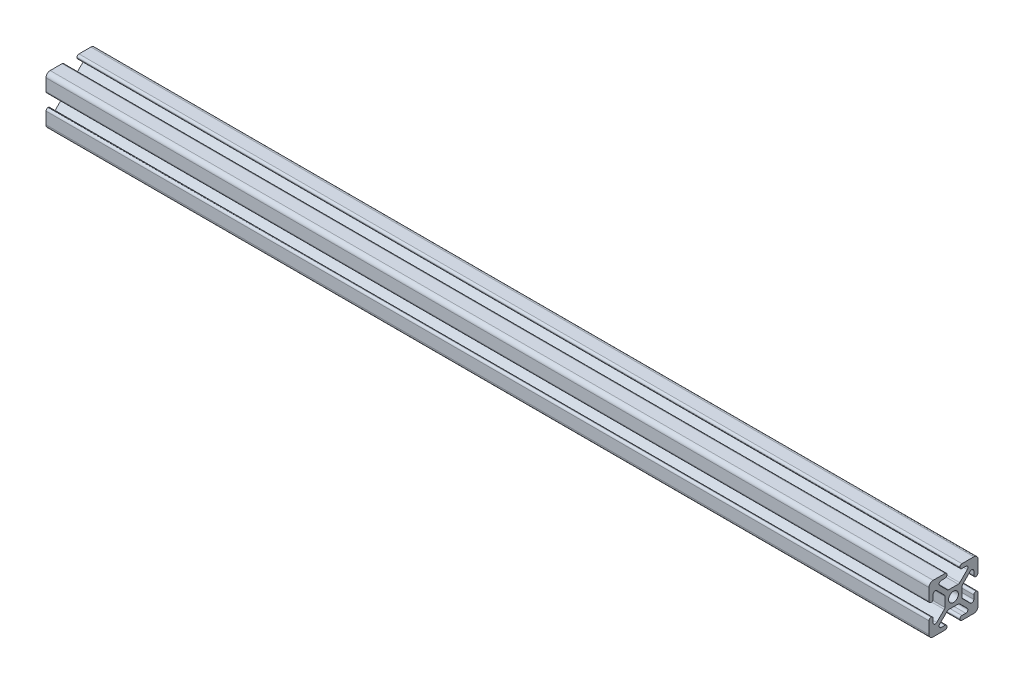
SolidWorks part; units mm, degrees
ref_plane "Front Plane" through (0, 0, 0) normal (1, 0, 0) x (0, 1, 0)
ref_plane "Top Plane" through (0, 0, 0) normal (0, 0, 1) x (0, 1, 0)
ref_plane "Right Plane" through (0, 0, 0) normal (0, 1, 0) x (-1, 0, 0)
sketch "Sketch1" plane through (0, 0, 0) normal (1, 0, 0) x (0, 1, 0)
  line L0 (0, 0) -> (0, 12.5) construction
  line L1 (-12.5, -12.5) -> (12.5, -12.5)
  line L2 (-12.5, -12.5) -> (-12.5, 12.5)
  line L3 (-12.5, 12.5) -> (12.5, 12.5)
  line L4 (12.5, -12.5) -> (12.5, 12.5)
  line L5 (-12.5, -12.5) -> (12.5, 12.5) construction
  line L6 (-12.5, 12.5) -> (12.5, -12.5) construction
  line L7 (-3.25, 12.5) -> (-3.25, 10.37)
  line L8 (-3.25, 10.37) -> (-8.8639, 10.37)
  line L9 (-8.8639, 10.37) -> (-2.8739, 4.38)
  line L10 (-2.8739, 4.38) -> (2.8739, 4.38)
  line L11 (8.8639, 10.37) -> (2.8739, 4.38)
  line L12 (3.25, 10.37) -> (8.8639, 10.37)
  line L13 (3.25, 12.5) -> (3.25, 10.37)
  line L14 (12.5, -3.25) -> (10.37, -3.25)
  line L15 (10.37, -3.25) -> (10.37, -8.8639)
  line L16 (10.37, -8.8639) -> (4.38, -2.8739)
  line L17 (4.38, 2.8739) -> (4.38, -2.8739)
  line L18 (10.37, 8.8639) -> (4.38, 2.8739)
  line L19 (10.37, 3.25) -> (10.37, 8.8639)
  line L20 (12.5, 3.25) -> (10.37, 3.25)
  line L21 (-3.25, -12.5) -> (-3.25, -10.37)
  line L22 (-3.25, -10.37) -> (-8.8639, -10.37)
  line L23 (-8.8639, -10.37) -> (-2.8739, -4.38)
  line L24 (2.8739, -4.38) -> (-2.8739, -4.38)
  line L25 (8.8639, -10.37) -> (2.8739, -4.38)
  line L26 (3.25, -10.37) -> (8.8639, -10.37)
  line L27 (3.25, -12.5) -> (3.25, -10.37)
  line L28 (-12.5, 3.25) -> (-10.37, 3.25)
  line L29 (-10.37, 3.25) -> (-10.37, 8.8639)
  line L30 (-10.37, 8.8639) -> (-4.38, 2.8739)
  line L31 (-4.38, -2.8739) -> (-4.38, 2.8739)
  line L32 (-10.37, -8.8639) -> (-4.38, -2.8739)
  line L33 (-10.37, -3.25) -> (-10.37, -8.8639)
  line L34 (-12.5, -3.25) -> (-10.37, -3.25)
  circle A0 centre (0, 0) radius 2.5
  point P0 (0, 0)
  point P15 (0, 4.38)
  dimension "D3" = 5
  dimension "D1" = 25
  dimension "D2" = 25
  dimension "D4" = 2.13
  dimension "D5" = 2.13
  dimension "D6" = 6.5
  dimension "D7" = 4.38
  dimension "D8" = 4
extrude "Boss-Extrude1" add sketch "Sketch1" along normal blind 450 contours L34 L2 L1 L21 L22 L23 L24 L25 L26 L27 L4 L14 L15 L16 L17 L18 L19 L20 L3 L13 L12 L11 L10 L9 L8 L7 L28 L29 L30 L31 L32 L33 A0 region at (0, -12.1464, -7.875)
fillet "Fillet1" radius 1.065 32 edges at (225, -10.37, -8.8639) (225, 2.8739, -4.38) (225, -2.8739, -4.38) (225, -4.38, 2.8739) (225, -4.38, -2.8739) (225, -2.8739, 4.38) (225, 2.8739, 4.38) (225, 4.38, 2.8739) (225, 4.38, -2.8739) (225, -8.8639, -10.37) (225, 8.8639, -10.37) (225, 10.37, -8.8639) (225, -10.37, 8.8639) (225, -8.8639, 10.37) (225, 10.37, 8.8639) (225, 8.8639, 10.37) (225, 12.5, 3.25) (225, -3.25, -12.5) (225, -10.37, 3.25) (225, 10.37, 3.25) (225, -10.37, -3.25) (225, -12.5, -3.25) (225, -12.5, 3.25) (225, 3.25, -10.37) (225, -3.25, -10.37) (225, 3.25, -12.5) (225, 10.37, -3.25) (225, 12.5, -3.25) (225, 3.25, 12.5) (225, 3.25, 10.37) (225, -3.25, 10.37) (225, -3.25, 12.5)
fillet "Fillet2" radius 2.13 4 edges at (225, 12.5, -12.5) (225, -12.5, -12.5) (225, 12.5, 12.5) (225, -12.5, 12.5)
sketch "Sketch2" plane through (450, 0, 0) normal (1, 0, 0) x (0, 1, 0)
  line L0 (10.37, -12.5) -> (4.315, -12.5)
  line L1 (10.37, -12.5) -> (4.315, -12.5)
  line L2 (4.315, -10.37) -> (6.2927, -10.37)
  line L3 (4.315, -10.37) -> (6.2927, -10.37)
  line L4 (7.0458, -8.5519) -> (3.1858, -4.6919)
  line L5 (7.0458, -8.5519) -> (3.1858, -4.6919)
  line L6 (2.4327, -4.38) -> (-2.4327, -4.38)
  line L7 (2.4327, -4.38) -> (-2.4327, -4.38)
  line L8 (-3.1858, -4.6919) -> (-7.0458, -8.5519)
  line L9 (-3.1858, -4.6919) -> (-7.0458, -8.5519)
  line L10 (-6.2927, -10.37) -> (-4.315, -10.37)
  line L11 (-6.2927, -10.37) -> (-4.315, -10.37)
  line L12 (-4.315, -12.5) -> (-10.37, -12.5)
  line L13 (-4.315, -12.5) -> (-10.37, -12.5)
  line L14 (-12.5, -10.37) -> (-12.5, -4.315)
  line L15 (-12.5, -10.37) -> (-12.5, -4.315)
  line L16 (-10.37, -4.315) -> (-10.37, -6.2927)
  line L17 (-10.37, -4.315) -> (-10.37, -6.2927)
  line L18 (-8.5519, -7.0458) -> (-4.6919, -3.1858)
  line L19 (-8.5519, -7.0458) -> (-4.6919, -3.1858)
  line L20 (-4.38, -2.4327) -> (-4.38, 2.4327)
  line L21 (-4.38, -2.4327) -> (-4.38, 2.4327)
  line L22 (-4.6919, 3.1858) -> (-8.5519, 7.0458)
  line L23 (-4.6919, 3.1858) -> (-8.5519, 7.0458)
  line L24 (-10.37, 6.2927) -> (-10.37, 4.315)
  line L25 (-10.37, 6.2927) -> (-10.37, 4.315)
  line L26 (-12.5, 4.315) -> (-12.5, 10.37)
  line L27 (-12.5, 4.315) -> (-12.5, 10.37)
  line L28 (-10.37, 12.5) -> (-4.315, 12.5)
  line L29 (-10.37, 12.5) -> (-4.315, 12.5)
  line L30 (-4.315, 10.37) -> (-6.2927, 10.37)
  line L31 (-4.315, 10.37) -> (-6.2927, 10.37)
  line L32 (-7.0458, 8.5519) -> (-3.1858, 4.6919)
  line L33 (-7.0458, 8.5519) -> (-3.1858, 4.6919)
  line L34 (-2.4327, 4.38) -> (2.4327, 4.38)
  line L35 (-2.4327, 4.38) -> (2.4327, 4.38)
  line L36 (3.1858, 4.6919) -> (7.0458, 8.5519)
  line L37 (3.1858, 4.6919) -> (7.0458, 8.5519)
  line L38 (6.2927, 10.37) -> (4.315, 10.37)
  line L39 (6.2927, 10.37) -> (4.315, 10.37)
  line L40 (4.315, 12.5) -> (10.37, 12.5)
  line L41 (4.315, 12.5) -> (10.37, 12.5)
  line L42 (12.5, 10.37) -> (12.5, 4.315)
  line L43 (12.5, 10.37) -> (12.5, 4.315)
  line L44 (10.37, 4.315) -> (10.37, 6.2927)
  line L45 (10.37, 4.315) -> (10.37, 6.2927)
  line L46 (8.5519, 7.0458) -> (4.6919, 3.1858)
  line L47 (8.5519, 7.0458) -> (4.6919, 3.1858)
  line L48 (4.38, 2.4327) -> (4.38, -2.4327)
  line L49 (4.38, 2.4327) -> (4.38, -2.4327)
  line L50 (4.6919, -3.1858) -> (8.5519, -7.0458)
  line L51 (4.6919, -3.1858) -> (8.5519, -7.0458)
  line L52 (10.37, -6.2927) -> (10.37, -4.315)
  line L53 (10.37, -6.2927) -> (10.37, -4.315)
  line L54 (12.5, -4.315) -> (12.5, -10.37)
  line L55 (12.5, -4.315) -> (12.5, -10.37)
  arc A0 (10.37, -12.5) -> (12.5, -10.37) centre (10.37, -10.37) ccw
  circle A1 centre (0, 0) radius 2.5
  circle A2 centre (0, 0) radius 2.5
  arc A3 (10.37, -12.5) -> (12.5, -10.37) centre (10.37, -10.37) ccw
  arc A4 (3.25, -11.435) -> (4.315, -12.5) centre (4.315, -11.435) ccw
  arc A5 (3.25, -11.435) -> (4.315, -12.5) centre (4.315, -11.435) ccw
  arc A6 (4.315, -10.37) -> (3.25, -11.435) centre (4.315, -11.435) ccw
  arc A7 (4.315, -10.37) -> (3.25, -11.435) centre (4.315, -11.435) ccw
  arc A8 (6.2927, -10.37) -> (7.0458, -8.5519) centre (6.2927, -9.305) ccw
  arc A9 (6.2927, -10.37) -> (7.0458, -8.5519) centre (6.2927, -9.305) ccw
  arc A10 (3.1858, -4.6919) -> (2.4327, -4.38) centre (2.4327, -5.445) ccw
  arc A11 (3.1858, -4.6919) -> (2.4327, -4.38) centre (2.4327, -5.445) ccw
  arc A12 (-2.4327, -4.38) -> (-3.1858, -4.6919) centre (-2.4327, -5.445) ccw
  arc A13 (-2.4327, -4.38) -> (-3.1858, -4.6919) centre (-2.4327, -5.445) ccw
  arc A14 (-7.0458, -8.5519) -> (-6.2927, -10.37) centre (-6.2927, -9.305) ccw
  arc A15 (-7.0458, -8.5519) -> (-6.2927, -10.37) centre (-6.2927, -9.305) ccw
  arc A16 (-3.25, -11.435) -> (-4.315, -10.37) centre (-4.315, -11.435) ccw
  arc A17 (-3.25, -11.435) -> (-4.315, -10.37) centre (-4.315, -11.435) ccw
  arc A18 (-4.315, -12.5) -> (-3.25, -11.435) centre (-4.315, -11.435) ccw
  arc A19 (-4.315, -12.5) -> (-3.25, -11.435) centre (-4.315, -11.435) ccw
  arc A20 (-12.5, -10.37) -> (-10.37, -12.5) centre (-10.37, -10.37) ccw
  arc A21 (-12.5, -10.37) -> (-10.37, -12.5) centre (-10.37, -10.37) ccw
  arc A22 (-11.435, -3.25) -> (-12.5, -4.315) centre (-11.435, -4.315) ccw
  arc A23 (-11.435, -3.25) -> (-12.5, -4.315) centre (-11.435, -4.315) ccw
  arc A24 (-10.37, -4.315) -> (-11.435, -3.25) centre (-11.435, -4.315) ccw
  arc A25 (-10.37, -4.315) -> (-11.435, -3.25) centre (-11.435, -4.315) ccw
  arc A26 (-10.37, -6.2927) -> (-8.5519, -7.0458) centre (-9.305, -6.2927) ccw
  arc A27 (-10.37, -6.2927) -> (-8.5519, -7.0458) centre (-9.305, -6.2927) ccw
  arc A28 (-4.6919, -3.1858) -> (-4.38, -2.4327) centre (-5.445, -2.4327) ccw
  arc A29 (-4.6919, -3.1858) -> (-4.38, -2.4327) centre (-5.445, -2.4327) ccw
  arc A30 (-4.38, 2.4327) -> (-4.6919, 3.1858) centre (-5.445, 2.4327) ccw
  arc A31 (-4.38, 2.4327) -> (-4.6919, 3.1858) centre (-5.445, 2.4327) ccw
  arc A32 (-8.5519, 7.0458) -> (-10.37, 6.2927) centre (-9.305, 6.2927) ccw
  arc A33 (-8.5519, 7.0458) -> (-10.37, 6.2927) centre (-9.305, 6.2927) ccw
  arc A34 (-11.435, 3.25) -> (-10.37, 4.315) centre (-11.435, 4.315) ccw
  arc A35 (-11.435, 3.25) -> (-10.37, 4.315) centre (-11.435, 4.315) ccw
  arc A36 (-12.5, 4.315) -> (-11.435, 3.25) centre (-11.435, 4.315) ccw
  arc A37 (-12.5, 4.315) -> (-11.435, 3.25) centre (-11.435, 4.315) ccw
  arc A38 (-10.37, 12.5) -> (-12.5, 10.37) centre (-10.37, 10.37) ccw
  arc A39 (-10.37, 12.5) -> (-12.5, 10.37) centre (-10.37, 10.37) ccw
  arc A40 (-3.25, 11.435) -> (-4.315, 12.5) centre (-4.315, 11.435) ccw
  arc A41 (-3.25, 11.435) -> (-4.315, 12.5) centre (-4.315, 11.435) ccw
  arc A42 (-4.315, 10.37) -> (-3.25, 11.435) centre (-4.315, 11.435) ccw
  arc A43 (-4.315, 10.37) -> (-3.25, 11.435) centre (-4.315, 11.435) ccw
  arc A44 (-6.2927, 10.37) -> (-7.0458, 8.5519) centre (-6.2927, 9.305) ccw
  arc A45 (-6.2927, 10.37) -> (-7.0458, 8.5519) centre (-6.2927, 9.305) ccw
  arc A46 (-3.1858, 4.6919) -> (-2.4327, 4.38) centre (-2.4327, 5.445) ccw
  arc A47 (-3.1858, 4.6919) -> (-2.4327, 4.38) centre (-2.4327, 5.445) ccw
  arc A48 (2.4327, 4.38) -> (3.1858, 4.6919) centre (2.4327, 5.445) ccw
  arc A49 (2.4327, 4.38) -> (3.1858, 4.6919) centre (2.4327, 5.445) ccw
  arc A50 (7.0458, 8.5519) -> (6.2927, 10.37) centre (6.2927, 9.305) ccw
  arc A51 (7.0458, 8.5519) -> (6.2927, 10.37) centre (6.2927, 9.305) ccw
  arc A52 (3.25, 11.435) -> (4.315, 10.37) centre (4.315, 11.435) ccw
  arc A53 (3.25, 11.435) -> (4.315, 10.37) centre (4.315, 11.435) ccw
  arc A54 (4.315, 12.5) -> (3.25, 11.435) centre (4.315, 11.435) ccw
  arc A55 (4.315, 12.5) -> (3.25, 11.435) centre (4.315, 11.435) ccw
  arc A56 (12.5, 10.37) -> (10.37, 12.5) centre (10.37, 10.37) ccw
  arc A57 (12.5, 10.37) -> (10.37, 12.5) centre (10.37, 10.37) ccw
  arc A58 (11.435, 3.25) -> (12.5, 4.315) centre (11.435, 4.315) ccw
  arc A59 (11.435, 3.25) -> (12.5, 4.315) centre (11.435, 4.315) ccw
  arc A60 (10.37, 4.315) -> (11.435, 3.25) centre (11.435, 4.315) ccw
  arc A61 (10.37, 4.315) -> (11.435, 3.25) centre (11.435, 4.315) ccw
  arc A62 (10.37, 6.2927) -> (8.5519, 7.0458) centre (9.305, 6.2927) ccw
  arc A63 (10.37, 6.2927) -> (8.5519, 7.0458) centre (9.305, 6.2927) ccw
  arc A64 (4.6919, 3.1858) -> (4.38, 2.4327) centre (5.445, 2.4327) ccw
  arc A65 (4.6919, 3.1858) -> (4.38, 2.4327) centre (5.445, 2.4327) ccw
  arc A66 (4.38, -2.4327) -> (4.6919, -3.1858) centre (5.445, -2.4327) ccw
  arc A67 (4.38, -2.4327) -> (4.6919, -3.1858) centre (5.445, -2.4327) ccw
  arc A68 (8.5519, -7.0458) -> (10.37, -6.2927) centre (9.305, -6.2927) ccw
  arc A69 (8.5519, -7.0458) -> (10.37, -6.2927) centre (9.305, -6.2927) ccw
  arc A70 (11.435, -3.25) -> (10.37, -4.315) centre (11.435, -4.315) ccw
  arc A71 (11.435, -3.25) -> (10.37, -4.315) centre (11.435, -4.315) ccw
  arc A72 (12.5, -4.315) -> (11.435, -3.25) centre (11.435, -4.315) ccw
  arc A73 (12.5, -4.315) -> (11.435, -3.25) centre (11.435, -4.315) ccw
  dimension "D1" = 0
